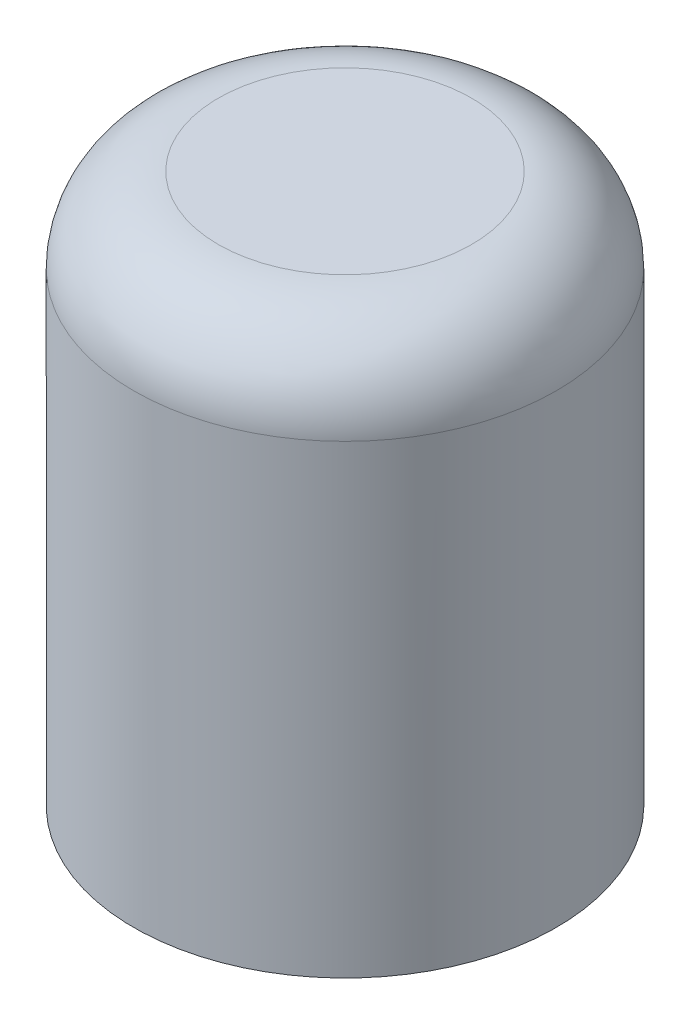
SolidWorks part; units mm, degrees
ref_plane "Front Plane" through (0, 0, 0) normal (0, 0, 1) x (1, 0, 0)
ref_plane "Top Plane" through (0, 0, 0) normal (0, 1, 0) x (1, 0, 0)
ref_plane "Right Plane" through (0, 0, 0) normal (1, 0, 0) x (0, 0, -1)
sketch "Sketch1" plane through (0, 0, 0) normal (0, 1, 0) x (1, 0, 0)
  circle A0 centre (0, 0) radius 5
  dimension "D1" = 10
extrude "Boss-Extrude1" add sketch "Sketch1" along normal blind 13
sketch "Insert" plane through (0, 0, 0) normal (0, -1, 0) x (1, 0, 0)
  line L0 (-2, 2.8723) -> (-2, -2.8723)
  line L1 (3.5, 0) -> (1.7771, 0) construction
  line L2 (-2, 0) -> (-0.8194, 0) construction
  arc A0 (-2, -2.8723) -> (-2, 2.8723) centre (0, 0) ccw
  dimension "D1" = 7
  dimension "D2" = 5.5
extrude "Cut-Extrude1" cut sketch "Insert" against normal blind 12.5
fillet "Fillet4" radius 2 2 edges at (3.5, 12.5, 0) (-2, 12.5, 0) type face fillet first side face at (-2, 6.25, 0) first side face at (0.75, 6.25, 0) second side face at (0.75, 12.5, 0)
fillet "Fillet5" radius 0.5 2 edges at (-2, 0, 0) (3.5, 0, 0) type face fillet first side face at (0.75, 0, 0) second side face at (0.75, 5.25, 0) second side face at (-2, 5.25, 0)
fillet "Fillet6" radius 2 1 edges at (0, 13, 5) type face fillet first side face at (0, 13, 5) second side face at (0, 13, 5)
